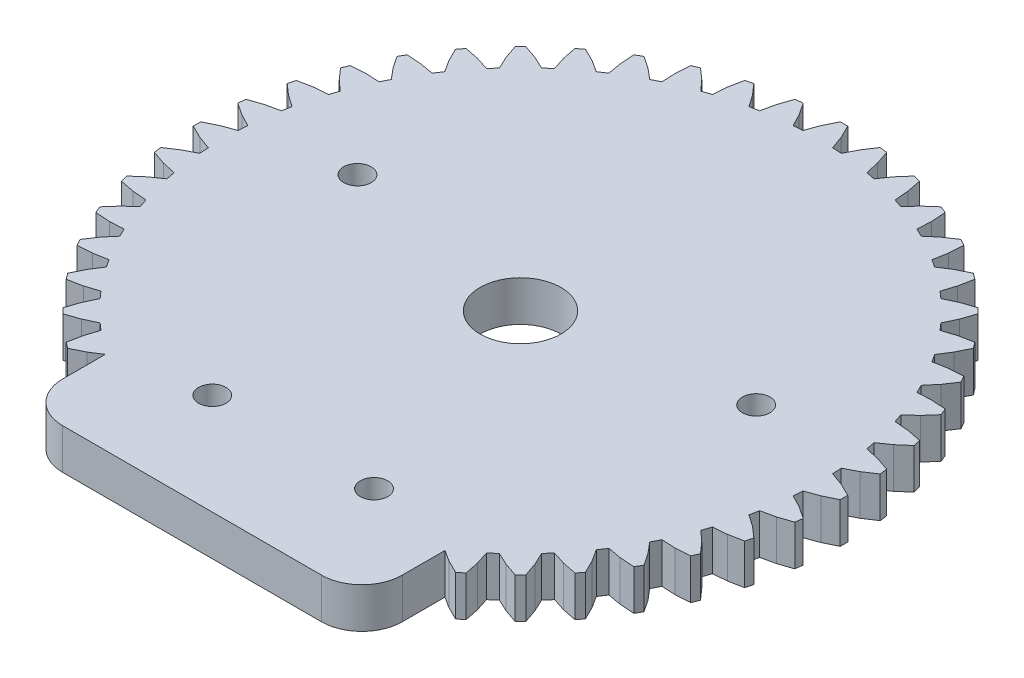
SolidWorks part; units mm, degrees
material "Acrylic (Medium-high impact)"
ref_plane "Front Plane" through (0, 0, 0) normal (0, 0, 1) x (1, 0, 0)
ref_plane "Top Plane" through (0, 0, 0) normal (0, 1, 0) x (1, 0, 0)
ref_plane "Right Plane" through (0, 0, 0) normal (1, 0, 0) x (0, 0, -1)
sketch "Sketch2" plane through (0, 0, 0) normal (0, 1, 0) x (1, 0, 0)
  line L0 (83.8835, 67.191) -> (85.5092, 66.6061)
  line L1 (85.5092, 66.6061) -> (87.1271, 65.8138)
  line L2 (87.1271, 65.8138) -> (87.1271, 64.8854)
  line L3 (87.1271, 64.8854) -> (85.5092, 64.0931)
  line L4 (85.5092, 64.0931) -> (83.8835, 63.5083)
  line L5 (83.8835, 63.5083) -> (83.8095, 62.3776)
  line L6 (83.8095, 62.3776) -> (85.3448, 61.5855)
  line L7 (85.3448, 61.5855) -> (86.8456, 60.5888)
  line L8 (86.8456, 60.5888) -> (86.7243, 59.6683)
  line L9 (86.7243, 59.6683) -> (85.0168, 59.094)
  line L10 (85.0168, 59.094) -> (83.3288, 58.7263)
  line L11 (83.3288, 58.7263) -> (83.1077, 57.615)
  line L12 (83.1077, 57.615) -> (84.5266, 56.6293)
  line L13 (84.5266, 56.6293) -> (85.8844, 55.4453)
  line L14 (85.8844, 55.4453) -> (85.6441, 54.5485)
  line L15 (85.6441, 54.5485) -> (83.8761, 54.202)
  line L16 (83.8761, 54.202) -> (82.1545, 54.0577)
  line L17 (82.1545, 54.0577) -> (81.7903, 52.9848)
  line L18 (81.7903, 52.9848) -> (83.0684, 51.8222)
  line L19 (83.0684, 51.8222) -> (84.26, 50.4711)
  line L20 (84.26, 50.4711) -> (83.9048, 49.6134)
  line L21 (83.9048, 49.6134) -> (82.1066, 49.5006)
  line L22 (82.1066, 49.5006) -> (80.3809, 49.5823)
  line L23 (80.3809, 49.5823) -> (79.8799, 48.5661)
  line L24 (79.8799, 48.5661) -> (80.9952, 47.2468)
  line L25 (80.9952, 47.2468) -> (82.0003, 45.7516)
  line L26 (82.0003, 45.7516) -> (81.5361, 44.9476)
  line L27 (81.5361, 44.9476) -> (79.7387, 45.0704)
  line L28 (79.7387, 45.0704) -> (78.0384, 45.3766)
  line L29 (78.0384, 45.3766) -> (77.4089, 44.4346)
  line L30 (77.4089, 44.4346) -> (78.3426, 42.9809)
  line L31 (78.3426, 42.9809) -> (79.1439, 41.3674)
  line L32 (79.1439, 41.3674) -> (78.5788, 40.6309)
  line L33 (78.5788, 40.6309) -> (76.8128, 40.9873)
  line L34 (76.8128, 40.9873) -> (75.167, 41.5128)
  line L35 (75.167, 41.5128) -> (74.4199, 40.6609)
  line L36 (74.4199, 40.6609) -> (75.1558, 39.0979)
  line L37 (75.1558, 39.0979) -> (75.7397, 37.3936)
  line L38 (75.7397, 37.3936) -> (75.0832, 36.737)
  line L39 (75.0832, 36.737) -> (73.3788, 37.3209)
  line L40 (73.3788, 37.3209) -> (71.8158, 38.0569)
  line L41 (71.8158, 38.0569) -> (70.9639, 37.3097)
  line L42 (70.9639, 37.3097) -> (71.4895, 35.6639)
  line L43 (71.4895, 35.6639) -> (71.8459, 33.898)
  line L44 (71.8459, 33.898) -> (71.1093, 33.3328)
  line L45 (71.1093, 33.3328) -> (69.4958, 34.1341)
  line L46 (69.4958, 34.1341) -> (68.0421, 35.0679)
  line L47 (68.0421, 35.0679) -> (67.1001, 34.4384)
  line L48 (67.1001, 34.4384) -> (67.4064, 32.738)
  line L49 (67.4064, 32.738) -> (67.5292, 30.9407)
  line L50 (67.5292, 30.9407) -> (66.7251, 30.4764)
  line L51 (66.7251, 30.4764) -> (65.23, 31.4815)
  line L52 (65.23, 31.4815) -> (63.9107, 32.5969)
  line L53 (63.9107, 32.5969) -> (62.8945, 32.0958)
  line L54 (62.8945, 32.0958) -> (62.9762, 30.3701)
  line L55 (62.9762, 30.3701) -> (62.8633, 28.572)
  line L56 (62.8633, 28.572) -> (62.0056, 28.2167)
  line L57 (62.0056, 28.2167) -> (60.6545, 29.4083)
  line L58 (60.6545, 29.4083) -> (59.4919, 30.6864)
  line L59 (59.4919, 30.6864) -> (58.419, 30.3222)
  line L60 (58.419, 30.3222) -> (58.2748, 28.6006)
  line L61 (58.2748, 28.6006) -> (57.9283, 26.8327)
  line L62 (57.9283, 26.8327) -> (57.0315, 26.5924)
  line L63 (57.0315, 26.5924) -> (55.8474, 27.9502)
  line L64 (55.8474, 27.9502) -> (54.8618, 29.369)
  line L65 (54.8618, 29.369) -> (53.7504, 29.1479)
  line L66 (53.7504, 29.1479) -> (53.3827, 27.4599)
  line L67 (53.3827, 27.4599) -> (52.8084, 25.7524)
  line L68 (52.8084, 25.7524) -> (51.888, 25.6311)
  line L69 (51.888, 25.6311) -> (50.8913, 27.1319)
  line L70 (50.8913, 27.1319) -> (50.0992, 28.6672)
  line L71 (50.0992, 28.6672) -> (48.9685, 28.5932)
  line L72 (48.9685, 28.5932) -> (48.3836, 26.9675)
  line L73 (48.3836, 26.9675) -> (47.5914, 25.3496)
  line L74 (47.5914, 25.3496) -> (46.6629, 25.3496)
  line L75 (46.6629, 25.3496) -> (45.8707, 26.9675)
  line L76 (45.8707, 26.9675) -> (45.2858, 28.5932)
  line L77 (45.2858, 28.5932) -> (44.1551, 28.6672)
  line L78 (44.1551, 28.6672) -> (43.363, 27.1319)
  line L79 (43.363, 27.1319) -> (42.3663, 25.6311)
  line L80 (42.3663, 25.6311) -> (41.4459, 25.7524)
  line L81 (41.4459, 25.7524) -> (40.8715, 27.4599)
  line L82 (40.8715, 27.4599) -> (40.5038, 29.1479)
  line L83 (40.5038, 29.1479) -> (39.3925, 29.369)
  line L84 (39.3925, 29.369) -> (38.4068, 27.9502)
  line L85 (38.4068, 27.9502) -> (37.2228, 26.5924)
  line L86 (37.2228, 26.5924) -> (36.326, 26.8327)
  line L87 (36.326, 26.8327) -> (35.9795, 28.6006)
  line L88 (35.9795, 28.6006) -> (35.8352, 30.3222)
  line L89 (35.8352, 30.3222) -> (34.7624, 30.6864)
  line L90 (34.7624, 30.6864) -> (33.5998, 29.4083)
  line L91 (33.5998, 29.4083) -> (32.2487, 28.2167)
  line L92 (32.2487, 28.2167) -> (31.3909, 28.572)
  line L93 (31.3909, 28.572) -> (31.2781, 30.3701)
  line L94 (31.2781, 30.3701) -> (31.3598, 32.0958)
  line L95 (31.3598, 32.0958) -> (30.3436, 32.5969)
  line L96 (30.3436, 32.5969) -> (29.0243, 31.4815)
  line L97 (29.0243, 31.4815) -> (27.5292, 30.4764)
  line L98 (27.5292, 30.4764) -> (26.7251, 30.9407)
  line L99 (26.7251, 30.9407) -> (26.8479, 32.738)
  line L100 (26.8479, 32.738) -> (27.1541, 34.4384)
  line L101 (27.1541, 34.4384) -> (26.2121, 35.0679)
  line L102 (26.2121, 35.0679) -> (24.7585, 34.1341)
  line L103 (24.7585, 34.1341) -> (23.1449, 33.3328)
  line L104 (23.1449, 33.3328) -> (22.4084, 33.898)
  line L105 (22.4084, 33.898) -> (22.7648, 35.6639)
  line L106 (22.7648, 35.6639) -> (23.2904, 37.3097)
  line L107 (23.2904, 37.3097) -> (22.4384, 38.0569)
  line L108 (22.4384, 38.0569) -> (20.8754, 37.3209)
  line L109 (20.8754, 37.3209) -> (19.1711, 36.737)
  line L110 (19.1711, 36.737) -> (18.5146, 37.3936)
  line L111 (18.5146, 37.3936) -> (19.0984, 39.0979)
  line L112 (19.0984, 39.0979) -> (19.8344, 40.6609)
  line L113 (19.8344, 40.6609) -> (19.0872, 41.5128)
  line L114 (19.0872, 41.5128) -> (17.4414, 40.9873)
  line L115 (17.4414, 40.9873) -> (15.6755, 40.6309)
  line L116 (15.6755, 40.6309) -> (15.1103, 41.3674)
  line L117 (15.1103, 41.3674) -> (15.9116, 42.9809)
  line L118 (15.9116, 42.9809) -> (16.8454, 44.4346)
  line L119 (16.8454, 44.4346) -> (16.2159, 45.3766)
  line L120 (16.2159, 45.3766) -> (14.5155, 45.0704)
  line L121 (14.5155, 45.0704) -> (12.7182, 44.9476)
  line L122 (12.7182, 44.9476) -> (12.2539, 45.7516)
  line L123 (12.2539, 45.7516) -> (13.2591, 47.2468)
  line L124 (13.2591, 47.2468) -> (14.3744, 48.5661)
  line L125 (14.3744, 48.5661) -> (13.8733, 49.5823)
  line L126 (13.8733, 49.5823) -> (12.1476, 49.5006)
  line L127 (12.1476, 49.5006) -> (10.3495, 49.6134)
  line L128 (10.3495, 49.6134) -> (9.9942, 50.4711)
  line L129 (9.9942, 50.4711) -> (11.1858, 51.8222)
  line L130 (11.1858, 51.8222) -> (12.4639, 52.9848)
  line L131 (12.4639, 52.9848) -> (12.0997, 54.0577)
  line L132 (12.0997, 54.0577) -> (10.3781, 54.202)
  line L133 (10.3781, 54.202) -> (8.6102, 54.5485)
  line L134 (8.6102, 54.5485) -> (8.3699, 55.4453)
  line L135 (8.3699, 55.4453) -> (9.7277, 56.6293)
  line L136 (9.7277, 56.6293) -> (11.1465, 57.615)
  line L137 (11.1465, 57.615) -> (10.9255, 58.7263)
  line L138 (10.9255, 58.7263) -> (9.2374, 59.094)
  line L139 (9.2374, 59.094) -> (7.5299, 59.6683)
  line L140 (7.5299, 59.6683) -> (7.4086, 60.5888)
  line L141 (7.4086, 60.5888) -> (8.9094, 61.5855)
  line L142 (8.9094, 61.5855) -> (10.4448, 62.3776)
  line L143 (10.4448, 62.3776) -> (10.3707, 63.5083)
  line L144 (10.3707, 63.5083) -> (8.745, 64.0931)
  line L145 (8.745, 64.0931) -> (7.1271, 64.8854)
  line L146 (7.1271, 64.8854) -> (7.1271, 65.8138)
  line L147 (7.1271, 65.8138) -> (8.745, 66.6061)
  line L148 (8.745, 66.6061) -> (10.3707, 67.191)
  line L149 (10.3707, 67.191) -> (10.4448, 68.3216)
  line L150 (10.4448, 68.3216) -> (8.9094, 69.1138)
  line L151 (8.9094, 69.1138) -> (7.4086, 70.1105)
  line L152 (7.4086, 70.1105) -> (7.5299, 71.0309)
  line L153 (7.5299, 71.0309) -> (9.2374, 71.6052)
  line L154 (9.2374, 71.6052) -> (10.9255, 71.9729)
  line L155 (10.9255, 71.9729) -> (11.1465, 73.0842)
  line L156 (11.1465, 73.0842) -> (9.7277, 74.0699)
  line L157 (9.7277, 74.0699) -> (8.3699, 75.254)
  line L158 (8.3699, 75.254) -> (8.6102, 76.1508)
  line L159 (8.6102, 76.1508) -> (10.3781, 76.4973)
  line L160 (10.3781, 76.4973) -> (12.0997, 76.6415)
  line L161 (12.0997, 76.6415) -> (12.4639, 77.7144)
  line L162 (12.4639, 77.7144) -> (11.1858, 78.877)
  line L163 (11.1858, 78.877) -> (9.9942, 80.2281)
  line L164 (9.9942, 80.2281) -> (10.3495, 81.0858)
  line L165 (10.3495, 81.0858) -> (12.1476, 81.1987)
  line L166 (12.1476, 81.1987) -> (13.8733, 81.117)
  line L167 (13.8733, 81.117) -> (14.3744, 82.1332)
  line L168 (14.3744, 82.1332) -> (13.2591, 83.4525)
  line L169 (13.2591, 83.4525) -> (12.2539, 84.9476)
  line L170 (12.2539, 84.9476) -> (12.7182, 85.7516)
  line L171 (12.7182, 85.7516) -> (14.5155, 85.6289)
  line L172 (14.5155, 85.6289) -> (16.2159, 85.3226)
  line L173 (16.2159, 85.3226) -> (16.8454, 86.2646)
  line L174 (16.8454, 86.2646) -> (15.9116, 87.7183)
  line L175 (15.9116, 87.7183) -> (15.1103, 89.3318)
  line L176 (15.1103, 89.3318) -> (15.6755, 90.0684)
  line L177 (15.6755, 90.0684) -> (17.4414, 89.712)
  line L178 (17.4414, 89.712) -> (19.0872, 89.1864)
  line L179 (19.0872, 89.1864) -> (19.8344, 90.0383)
  line L180 (19.8344, 90.0383) -> (19.0984, 91.6013)
  line L181 (19.0984, 91.6013) -> (18.5146, 93.3057)
  line L182 (18.5146, 93.3057) -> (19.1711, 93.9622)
  line L183 (19.1711, 93.9622) -> (20.8754, 93.3783)
  line L184 (20.8754, 93.3783) -> (22.4384, 92.6424)
  line L185 (22.4384, 92.6424) -> (23.2904, 93.3895)
  line L186 (23.2904, 93.3895) -> (22.7648, 95.0353)
  line L187 (22.7648, 95.0353) -> (22.4084, 96.8013)
  line L188 (22.4084, 96.8013) -> (23.1449, 97.3664)
  line L189 (23.1449, 97.3664) -> (24.7585, 96.5651)
  line L190 (24.7585, 96.5651) -> (26.2121, 95.6314)
  line L191 (26.2121, 95.6314) -> (27.1541, 96.2609)
  line L192 (27.1541, 96.2609) -> (26.8479, 97.9612)
  line L193 (26.8479, 97.9612) -> (26.7251, 99.7586)
  line L194 (26.7251, 99.7586) -> (27.5292, 100.2228)
  line L195 (27.5292, 100.2228) -> (29.0243, 99.2177)
  line L196 (29.0243, 99.2177) -> (30.3436, 98.1023)
  line L197 (30.3436, 98.1023) -> (31.3598, 98.6034)
  line L198 (31.3598, 98.6034) -> (31.2781, 100.3291)
  line L199 (31.2781, 100.3291) -> (31.3909, 102.1272)
  line L200 (31.3909, 102.1272) -> (32.2487, 102.4825)
  line L201 (32.2487, 102.4825) -> (33.5998, 101.2909)
  line L202 (33.5998, 101.2909) -> (34.7624, 100.0128)
  line L203 (34.7624, 100.0128) -> (35.8352, 100.377)
  line L204 (35.8352, 100.377) -> (35.9795, 102.0986)
  line L205 (35.9795, 102.0986) -> (36.326, 103.8666)
  line L206 (36.326, 103.8666) -> (37.2228, 104.1068)
  line L207 (37.2228, 104.1068) -> (38.4068, 102.7491)
  line L208 (38.4068, 102.7491) -> (39.3925, 101.3302)
  line L209 (39.3925, 101.3302) -> (40.5038, 101.5513)
  line L210 (40.5038, 101.5513) -> (40.8715, 103.2393)
  line L211 (40.8715, 103.2393) -> (41.4459, 104.9468)
  line L212 (41.4459, 104.9468) -> (42.3663, 105.0681)
  line L213 (42.3663, 105.0681) -> (43.363, 103.5673)
  line L214 (43.363, 103.5673) -> (44.1551, 102.032)
  line L215 (44.1551, 102.032) -> (45.2858, 102.106)
  line L216 (45.2858, 102.106) -> (45.8707, 103.7317)
  line L217 (45.8707, 103.7317) -> (46.6629, 105.3496)
  line L218 (46.6629, 105.3496) -> (47.5914, 105.3496)
  line L219 (47.5914, 105.3496) -> (48.3836, 103.7317)
  line L220 (48.3836, 103.7317) -> (48.9685, 102.106)
  line L221 (48.9685, 102.106) -> (50.0992, 102.032)
  line L222 (50.0992, 102.032) -> (50.8913, 103.5673)
  line L223 (50.8913, 103.5673) -> (51.888, 105.0681)
  line L224 (51.888, 105.0681) -> (52.8084, 104.9468)
  line L225 (52.8084, 104.9468) -> (53.3827, 103.2393)
  line L226 (53.3827, 103.2393) -> (53.7504, 101.5513)
  line L227 (53.7504, 101.5513) -> (54.8618, 101.3302)
  line L228 (54.8618, 101.3302) -> (55.8474, 102.7491)
  line L229 (55.8474, 102.7491) -> (57.0315, 104.1068)
  line L230 (57.0315, 104.1068) -> (57.9283, 103.8666)
  line L231 (57.9283, 103.8666) -> (58.2748, 102.0986)
  line L232 (58.2748, 102.0986) -> (58.419, 100.377)
  line L233 (58.419, 100.377) -> (59.4919, 100.0128)
  line L234 (59.4919, 100.0128) -> (60.6545, 101.2909)
  line L235 (60.6545, 101.2909) -> (62.0056, 102.4825)
  line L236 (62.0056, 102.4825) -> (62.8633, 102.1272)
  line L237 (62.8633, 102.1272) -> (62.9762, 100.3291)
  line L238 (62.9762, 100.3291) -> (62.8945, 98.6034)
  line L239 (62.8945, 98.6034) -> (63.9107, 98.1023)
  line L240 (63.9107, 98.1023) -> (65.23, 99.2177)
  line L241 (65.23, 99.2177) -> (66.7251, 100.2228)
  line L242 (66.7251, 100.2228) -> (67.5292, 99.7586)
  line L243 (67.5292, 99.7586) -> (67.4064, 97.9612)
  line L244 (67.4064, 97.9612) -> (67.1001, 96.2609)
  line L245 (67.1001, 96.2609) -> (68.0421, 95.6314)
  line L246 (68.0421, 95.6314) -> (69.4958, 96.5651)
  line L247 (69.4958, 96.5651) -> (71.1093, 97.3664)
  line L248 (71.1093, 97.3664) -> (71.8459, 96.8013)
  line L249 (71.8459, 96.8013) -> (71.4895, 95.0353)
  line L250 (71.4895, 95.0353) -> (70.9639, 93.3895)
  line L251 (70.9639, 93.3895) -> (71.8158, 92.6424)
  line L252 (71.8158, 92.6424) -> (73.3788, 93.3783)
  line L253 (73.3788, 93.3783) -> (75.0832, 93.9622)
  line L254 (75.0832, 93.9622) -> (75.7397, 93.3057)
  line L255 (75.7397, 93.3057) -> (75.1558, 91.6013)
  line L256 (75.1558, 91.6013) -> (74.4199, 90.0383)
  line L257 (74.4199, 90.0383) -> (75.167, 89.1864)
  line L258 (75.167, 89.1864) -> (76.8128, 89.712)
  line L259 (76.8128, 89.712) -> (78.5788, 90.0684)
  line L260 (78.5788, 90.0684) -> (79.1439, 89.3318)
  line L261 (79.1439, 89.3318) -> (78.3426, 87.7183)
  line L262 (78.3426, 87.7183) -> (77.4089, 86.2646)
  line L263 (77.4089, 86.2646) -> (78.0384, 85.3226)
  line L264 (78.0384, 85.3226) -> (79.7387, 85.6289)
  line L265 (79.7387, 85.6289) -> (81.5361, 85.7516)
  line L266 (81.5361, 85.7516) -> (82.0003, 84.9476)
  line L267 (82.0003, 84.9476) -> (80.9952, 83.4525)
  line L268 (80.9952, 83.4525) -> (79.8799, 82.1332)
  line L269 (79.8799, 82.1332) -> (80.3809, 81.117)
  line L270 (80.3809, 81.117) -> (82.1066, 81.1987)
  line L271 (82.1066, 81.1987) -> (83.9048, 81.0858)
  line L272 (83.9048, 81.0858) -> (84.26, 80.2281)
  line L273 (84.26, 80.2281) -> (83.0684, 78.877)
  line L274 (83.0684, 78.877) -> (81.7903, 77.7144)
  line L275 (81.7903, 77.7144) -> (82.1545, 76.6415)
  line L276 (82.1545, 76.6415) -> (83.8761, 76.4973)
  line L277 (83.8761, 76.4973) -> (85.6441, 76.1508)
  line L278 (85.6441, 76.1508) -> (85.8844, 75.254)
  line L279 (85.8844, 75.254) -> (84.5266, 74.0699)
  line L280 (84.5266, 74.0699) -> (83.1077, 73.0842)
  line L281 (83.1077, 73.0842) -> (83.3288, 71.9729)
  line L282 (83.3288, 71.9729) -> (85.0168, 71.6052)
  line L283 (85.0168, 71.6052) -> (86.7243, 71.0309)
  line L284 (86.7243, 71.0309) -> (86.8456, 70.1105)
  line L285 (86.8456, 70.1105) -> (85.3448, 69.1138)
  line L286 (85.3448, 69.1138) -> (83.8095, 68.3216)
  line L287 (83.8095, 68.3216) -> (83.8835, 67.191)
  line L288 (47.1271, 105.3496) -> (47.1271, 25.3496) construction
  line L289 (7.1271, 65.3496) -> (87.1271, 65.3496) construction
  circle A0 centre (47.1271, 65.3496) radius 5
  point P292 (47.1271, 65.3496)
  dimension "D1" = 10
sketch "Sketch7" plane through (0, 0, 0) normal (0, 1, 0) x (1, 0, 0)
  line L0 (47.1271, 65.3496) -> (47.1271, 5.5554) construction
  line L1 (47.1271, 105.3496) -> (47.1271, 25.3496) construction
  circle A0 centre (37.1271, 37.2366) radius 1.7
  circle A1 centre (57.1271, 37.2366) radius 1.7
  dimension "D3" = 3.4
  dimension "D1" = 20
  dimension "D2" = 28.113
sketch "Sketch8" plane through (0, 0, 0) normal (0, 1, 0) x (1, 0, 0)
  line L0 (37.1271, 37.2366) -> (57.1271, 37.2366) construction
  line L2 (26.1271, 49.7366) -> (68.1271, 49.7366)
  line L3 (26.1271, 49.7366) -> (26.1271, 24.7366)
  line L4 (26.1271, 24.7366) -> (68.1271, 24.7366)
  line L5 (68.1271, 49.7366) -> (68.1271, 24.7366)
  line L6 (26.1271, 49.7366) -> (68.1271, 24.7366) construction
  line L7 (26.1271, 24.7366) -> (68.1271, 49.7366) construction
  point P4 (47.1271, 37.2366)
  dimension "D1" = 42
  dimension "D2" = 25
extrude "Boss-Extrude3" add sketch "Sketch2" along normal blind 5
extrude "Boss-Extrude4" add sketch "Sketch8" along normal up to surface (5 mm away) up to face at (47.1271, 5, -65.3496)
extrude "Cut-Extrude1" cut sketch "Sketch7" along normal through all
sketch "Sketch10" plane through (0, 0, 0) normal (0, -1, 0) x (1, 0, 0)
  circle A0 centre (71.7771, -69.8366) radius 1.7
  circle A1 centre (22.4771, -69.8366) radius 1.7
  circle A2 centre (22.4771, -69.8366) radius 1.7 construction
  circle A3 centre (71.7771, -69.8366) radius 1.7 construction
extrude "Cut-Extrude2" cut sketch "Sketch10" against normal up to next
fillet "Fillet1" radius 5 2 edges at (68.1271, 2.5, -24.7366) (26.1271, 2.5, -24.7366)
ref_axis "Axis5" through (47.1271, 5, -65.3496) along (0, -1, 0)
